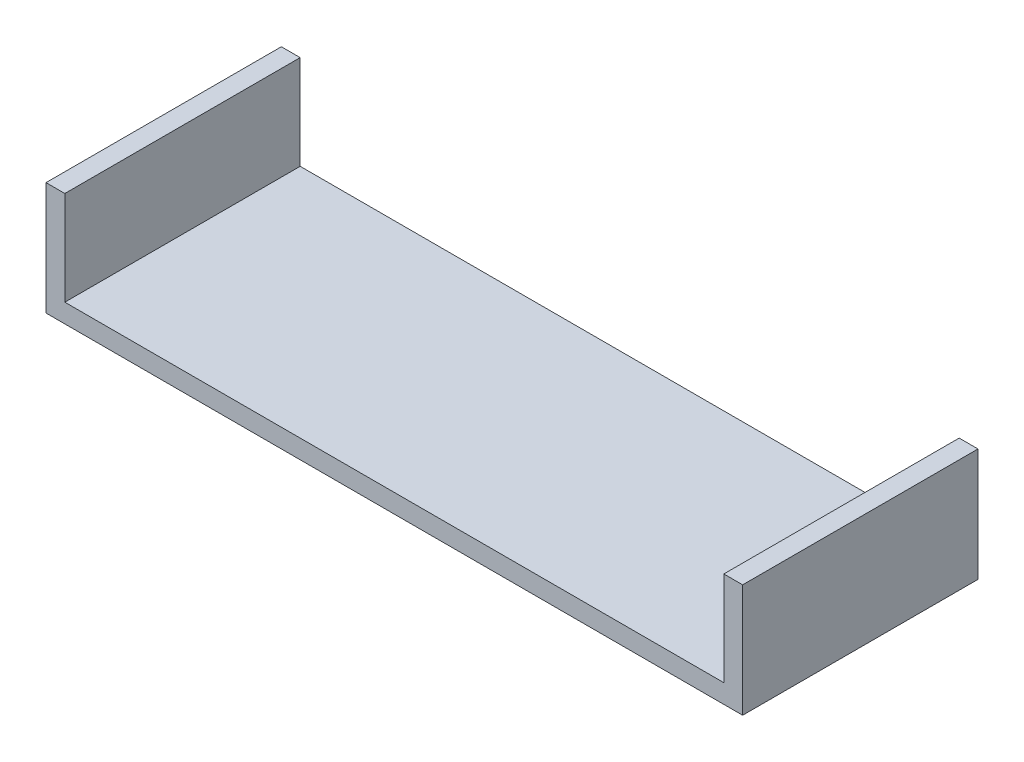
SolidWorks part; units mm, degrees
ref_plane "Front Plane" through (0, 0, 0) normal (0, 0, 1) x (1, 0, 0)
ref_plane "Top Plane" through (0, 0, 0) normal (0, 1, 0) x (1, 0, 0)
ref_plane "Right Plane" through (0, 0, 0) normal (1, 0, 0) x (0, 0, -1)
sketch "Sketch1" plane through (0, 0, 0) normal (0, 0, 1) x (1, 0, 0)
  line L0 (-939.8, 0) -> (939.8, 0)
  line L1 (-939.8, 0) -> (-939.8, 304.8)
  line L2 (-939.8, 304.8) -> (-889, 304.8)
  line L3 (-889, 304.8) -> (-889, 50.8)
  line L4 (-889, 50.8) -> (889, 50.8)
  line L5 (0, 50.8) -> (0, 0) construction
  line L6 (939.8, 0) -> (939.8, 304.8)
  line L7 (939.8, 304.8) -> (889, 304.8)
  line L8 (889, 304.8) -> (889, 50.8)
  dimension "D1" = 50.8
  dimension "D2" = 50.8
  dimension "D3" = 254
  dimension "D4" = 889
extrude "Boss-Extrude1" add sketch "Sketch1" along normal mid plane 635 contours L4 L8 L7 L6 L0 L1 L2 L3
ref_point "Point1"
ref_point "Point2"
ref_axis "Axis1" through (939.8, 0, 0) along (-1, 0, 0)
equation "\"D2@Sketch1\"=\"D1@Sketch1\""
